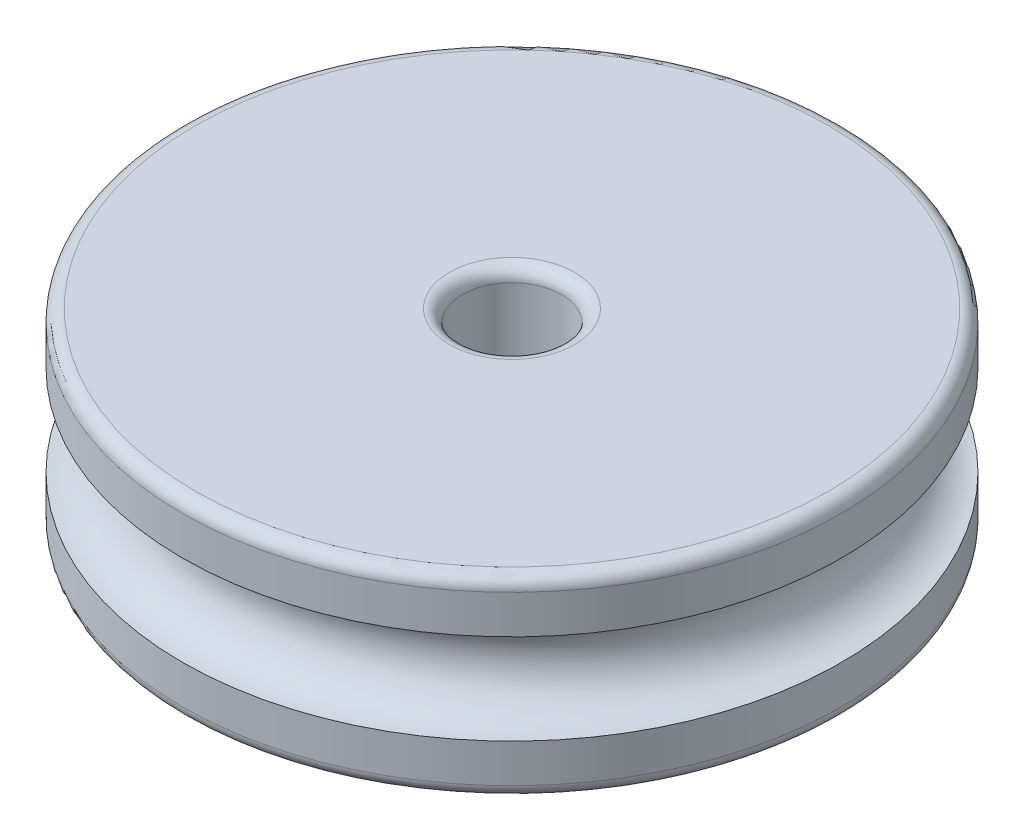
SolidWorks part; units mm, degrees
ref_plane "Front Plane" through (0, 0, 0) normal (0, 0, 1) x (1, 0, 0)
ref_plane "Top Plane" through (0, 0, 0) normal (0, 1, 0) x (1, 0, 0)
ref_plane "Right Plane" through (0, 0, 0) normal (1, 0, 0) x (0, 0, -1)
sketch "Croquis1" plane through (0, 0, 0) normal (0, 1, 0) x (1, 0, 0)
  circle A2 centre (0, 0) radius 25.58
  circle A3 centre (0, 0) radius 3.86
  dimension "D3" = 51.16
  dimension "D4" = 7.72
extrude "Saliente-Extruir1" add sketch "Croquis1" along normal blind 7.5 and the other way blind 7.5 contours A2 A3 region at (-24.8565, 0, 0)
sketch "Croquis2" plane through (0, 0, 0) normal (0, 0, 1) x (1, 0, 0)
  line L0 (-25.58, 7.5) -> (-25.58, -7.5) construction
  circle A0 centre (-25.58, 0) radius 3.505
  dimension "D1" = 7.01
sketch "Croquis3" plane through (0, 0, 0) normal (0, 1, 0) x (1, 0, 0)
  circle A0 centre (0, 0) radius 25.68
  dimension "D1" = 51.36
sweep "Cortar-Barrer1" cut profiles "Croquis2" path "Croquis1<4>"
sketch "Croquis1<4>" plane through (0, 0, 0) normal (0, 1, 0) x (1, 0, 0) same geometry as "Croquis1"
fillet "Redondeo1" radius 1 4 edges at (0, -7.5, 25.58) (0, 7.5, 25.58) (0, 7.5, 3.86) (0, -7.5, 3.86)
